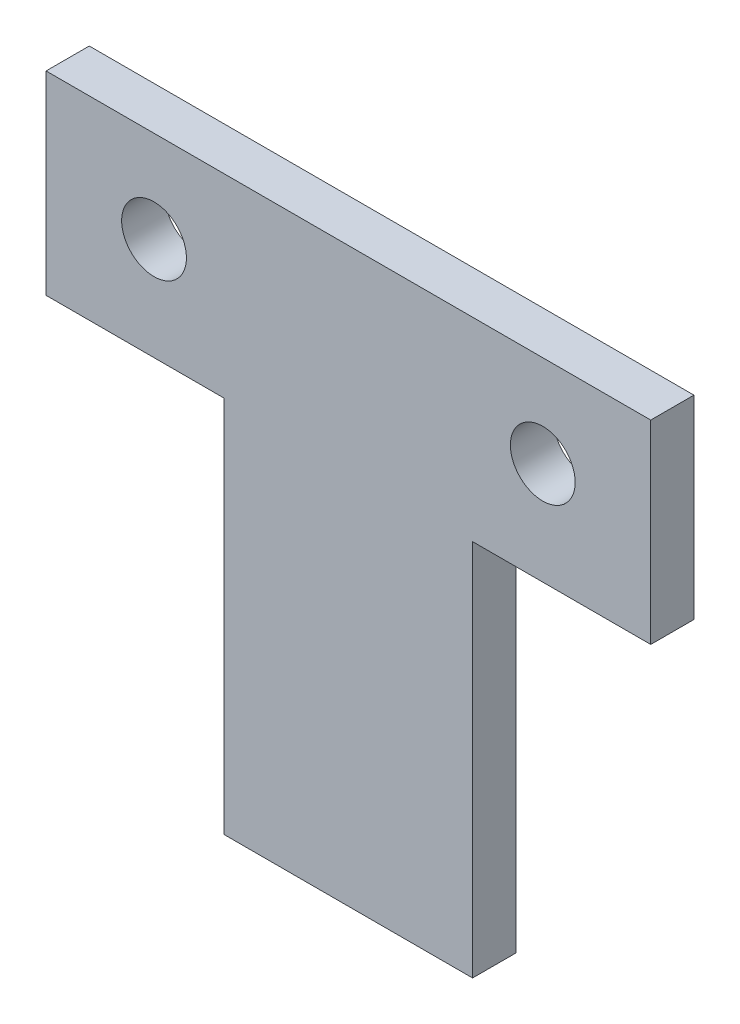
SolidWorks part; units mm, degrees
ref_plane "Front Plane" through (0, 0, 0) normal (0, 0, 1) x (1, 0, 0)
ref_plane "Top Plane" through (0, 0, 0) normal (0, 1, 0) x (1, 0, 0)
ref_plane "Right Plane" through (0, 0, 0) normal (1, 0, 0) x (0, 0, -1)
sketch "Sketch1" plane through (0, 0, 0) normal (0, 0, 1) x (1, 0, 0)
  line L0 (5, 4.75) -> (23, 4.75) construction
  line L1 (0, 0) -> (28, 0)
  line L2 (0, 0) -> (0, 9)
  line L3 (0, 9) -> (28, 9)
  line L4 (28, 0) -> (28, 9)
  line L5 (12.5, 0) -> (15.5, 0)
  line L7 (12.5, -17.5) -> (15.5, -17.5)
  line L13 (14, -14.9351) -> (14, -17.5)
  line L14 (14, -17.5) -> (19.75, -17.5)
  line L15 (19.75, -17.5) -> (19.75, 0)
  line L16 (14, -17.5) -> (8.25, -17.5)
  line L17 (8.25, -17.5) -> (8.25, 0)
  circle A0 centre (5, 4.75) radius 1.5
  circle A1 centre (23, 4.75) radius 1.5
  point P9 (14, 0)
  point P15 (5, 4.75)
  point P16 (23, 4.75)
  point P19 (14, 4.75)
  point P20 (14, 9)
  dimension "D9" = 3
  dimension "D1" = 28
  dimension "D2" = 9
  dimension "D3" = 3
  dimension "D4" = 17.5
  dimension "D7" = 4.25
  dimension "D8" = 18
extrude "Boss-Extrude1" add sketch "Sketch1" along normal blind 2 contours L1 L4 L3 L2 A0 A1 | L1 | L7 region at (14, 4.4851, 0) region at (14, -8.75, 0)
